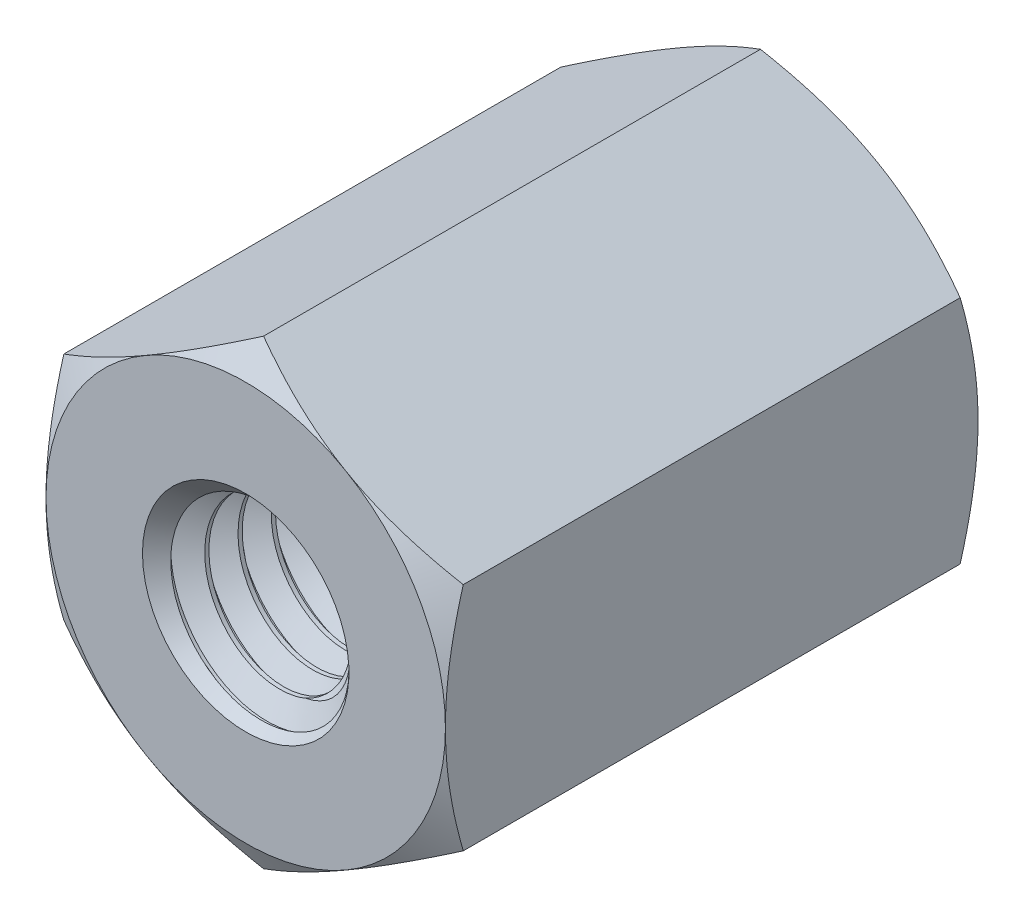
SolidWorks part; units mm, degrees
ref_plane "Front Plane" through (0, 0, 0) normal (0, 0, 1) x (1, 0, 0)
ref_plane "Top Plane" through (0, 0, 0) normal (0, 1, 0) x (1, 0, 0)
ref_plane "Right Plane" through (0, 0, 0) normal (1, 0, 0) x (0, 0, -1)
sketch "Sketch3" plane through (0, 0, 0) normal (1, 0, 0) x (0, 0, -1)
  line L0 (-4, 0) -> (4, 0) construction
  line L1 (0, 3) -> (0, -3) construction
  line L2 (-4, 1.5) -> (-4, -1.5) construction
  point P2 (-0.8, 0)
  point P3 (0.8, 0)
  dimension "Length" = 8
  dimension "Min Thread Length" = 4.8
  dimension "D1" = 4.8
  dimension "Thread Dia" = 3
  dimension "Hex" = 6
sketch "Sketch1" plane through (0, 0, 0) normal (0, 0, 1) x (1, 0, 0)
  line L1 (0, 3.4641) -> (-3, 1.7321)
  line L2 (-3, 1.7321) -> (-3, -1.7321)
  line L3 (-3, -1.7321) -> (0, -3.4641)
  line L4 (0, -3.4641) -> (3, -1.7321)
  line L5 (3, -1.7321) -> (3, 1.7321)
  line L6 (3, 1.7321) -> (0, 3.4641)
  circle A0 centre (0, 0) radius 3 construction
  circle A1 centre (0, 0) radius 1.5
extrude "Extrude1" add sketch "Sketch1" along normal up to vertex (4 mm away) and the other way up to vertex (4 mm away) up to point (0, 0, 4) other way up to point (0, 0, -4)
sketch "Sketch11" plane through (0, 0, -4) normal (0, 0, -1) x (-1, 0, 0)
  circle A0 centre (0, 0) radius 1.5 construction
  circle A1 centre (0, 0) radius 1.5
curve "Helix/Spiral1" pitch 0.5 height 8.5 radius 1.5 centre (0, 0, -4) axis (0, 0, 1) start towards (0, 1, 0) parameters "Pitch"=0.5
sketch "Sketch12" plane through (0, 0, 0) normal (1, 0, 0) x (0, 0, -1)
  line L0 (4.4375, 1.5) -> (4, 1.5)
  line L1 (4.4375, 1.5) -> (4.25, 1.1752)
  line L2 (4.25, 1.1752) -> (4.1875, 1.1752)
  line L3 (4.1875, 1.1752) -> (4, 1.5)
  line L4 (4.2188, 1.1752) -> (4.2188, 1.5) construction
  line L5 (4.3438, 1.3376) -> (4.0938, 1.3376) construction
  dimension "D1" = 0.0625
  dimension "D2" = 0.25
  dimension "D3" = 60
sweep "Sweep1" add profiles "Sketch12" path "Helix/Spiral1"
sketch "Sketch6" plane through (0, 0, -4) normal (0, 0, -1) x (-1, 0, 0)
  line L6 (0, 3.4641) -> (-3, 1.7321)
  line L7 (-3, 1.7321) -> (-3, -1.7321)
  line L8 (-3, -1.7321) -> (0, -3.4641)
  line L9 (0, -3.4641) -> (3, -1.7321)
  line L10 (3, -1.7321) -> (3, 1.7321)
  line L11 (3, 1.7321) -> (0, 3.4641)
  line L12 (0, 3.4641) -> (-3, 1.7321)
  line L13 (-3, 1.7321) -> (-3, -1.7321)
  line L14 (-3, -1.7321) -> (0, -3.4641)
  line L15 (0, -3.4641) -> (3, -1.7321)
  line L16 (3, -1.7321) -> (3, 1.7321)
  line L17 (3, 1.7321) -> (0, 3.4641)
  dimension "D1" = 0
extrude "Extrude2" cut sketch "Sketch6" along normal through all
sketch "Sketch7" plane through (0, 0, -4) normal (0, 0, -1) x (-1, 0, 0)
  circle A2 centre (0, 0) radius 1.5508
  circle A3 centre (0, 0) radius 1.5508
  dimension "D1" = 0.0508
extrude "Extrude3" cut sketch "Sketch7" against normal through all draft 43
sketch "Sketch8" plane through (0, 0, -4) normal (0, 0, -1) x (-1, 0, 0)
  circle A0 centre (0, 0) radius 3 construction
  circle A1 centre (0, 0) radius 3
extrude "Extrude4" cut sketch "Sketch8" against normal through all draft 60 flip side to cut
mirror "Mirror1" about plane through (0, 0, 0) normal (0, 0, 1) of "Extrude2", "Extrude3", "Extrude4"
sketch "Sketch9" [suppressed] plane through (0, 0, 0) normal (1, 0, 0) x (0, 0, -1)
  line L1 (-1.2, 1.1353) -> (1.2, 1.1353)
  line L2 (-1.2, 1.1353) -> (-1.2, 0)
  line L3 (-1.2, 0) -> (1.2, 0)
  line L4 (1.2, 1.1353) -> (1.2, 0)
  line L7 (-6, 0) -> (6, 0) construction
revolve "Revolve" [suppressed] add sketch "Sketch9" angle 360 about L0
sketch "Sketch10" [suppressed] plane through (0, 0, 0) normal (1, 0, 0) x (0, 0, -1)
  line L0 (6, 1.25) -> (1.2, 1.25)
  line L1 (-6, 1.25) -> (-1.2, 1.25)
  line L2 (1.2, 1.25) -> (1.2, -1.25)
  line L3 (-6, -1.25) -> (-1.2, -1.25)
  line L4 (-1.2, 1.25) -> (-1.2, -1.25)
  line L5 (1.2, -1.25) -> (6, -1.25)
equation "\"D1@Sketch3\" = \"Min Thread Length@Sketch3\""
equation "\"D3@Helix/Spiral1\" = \"Length@Sketch3\"+\"Pitch@Helix/Spiral1\""
equation "\"D1@Sketch12\" = \"Pitch@Helix/Spiral1\"*.125"
equation "\"D2@Sketch12\" = \"Pitch@Helix/Spiral1\"*.5"
